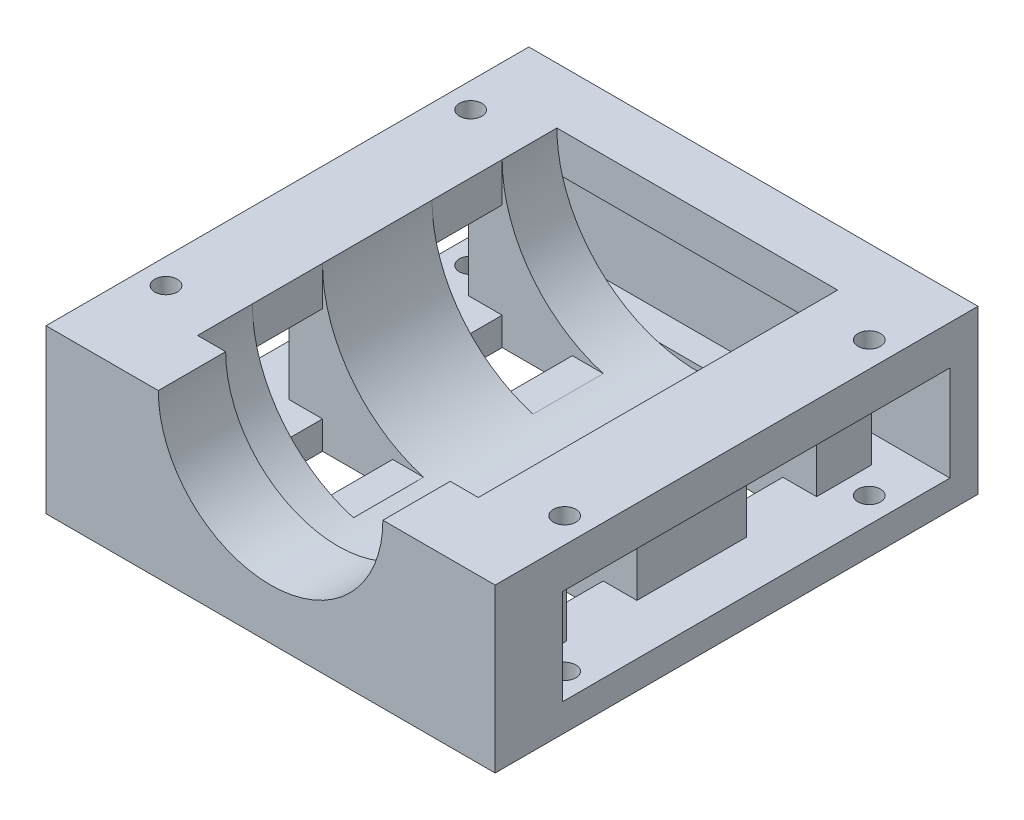
SolidWorks part; units mm, degrees
ref_plane "Front Plane" through (0, 0, 0) normal (0, 0, 1) x (1, 0, 0)
ref_plane "Top Plane" through (0, 0, 0) normal (0, 1, 0) x (1, 0, 0)
ref_plane "Right Plane" through (0, 0, 0) normal (1, 0, 0) x (0, 0, -1)
sketch "Sketch1" plane through (0, 0, 0) normal (0, 0, 1) x (1, 0, 0)
  line L0 (0, 0) -> (80, 0)
  line L1 (80, 0) -> (80, 5)
  line L2 (80, 5) -> (71, 5)
  line L3 (71, 5) -> (71, 22)
  line L4 (80, 29) -> (65, 29)
  line L7 (15, 29) -> (0, 29)
  line L8 (9, 22) -> (9, 5)
  line L9 (9, 5) -> (0, 5)
  line L10 (0, 5) -> (0, 0)
  line L12 (0, 29) -> (0, 22)
  line L13 (0, 22) -> (9, 22)
  line L14 (80, 29) -> (80, 22)
  line L15 (80, 22) -> (71, 22)
  arc A0 (15, 29) -> (65, 29) centre (40, 29) ccw
  dimension "D1" = 50
  dimension "D2" = 9
  dimension "D3" = 5
  dimension "D4" = 7
  dimension "D5" = 15
  dimension "D6" = 17
extrude "Boss-Extrude1" add sketch "Sketch1" along normal blind 64
ref_plane "Plane1" through (0, 0, 64) normal (0, 0, 1) x (1, 0, 0)
sketch "Sketch2" plane through (0, 0, 64) normal (0, 0, 1) x (1, 0, 0)
  line L0 (60, 29) -> (80, 29)
  line L1 (0, 0) -> (80, 0)
  line L2 (0, 0) -> (0, 29)
  line L3 (0, 29) -> (20, 29)
  line L4 (80, 0) -> (80, 29)
  line L5 (40, 0) -> (40, 29) construction
  arc A0 (20, 29) -> (60, 29) centre (40, 29) ccw
  dimension "D1" = 40
extrude "Boss-Extrude2" add sketch "Sketch2" along normal blind 12
ref_plane "Plane2" through (0, 29, 0) normal (0, 1, 0) x (1, 0, 0)
sketch "Sketch3" plane through (0, 29, 0) normal (0, 1, 0) x (1, 0, 0)
  line L0 (15, -64) -> (15, 0) construction
  line L1 (15, -9.75) -> (27.5, -9.75)
  line L2 (15, -9.75) -> (15, -22.25)
  line L3 (15, -22.25) -> (27.5, -22.25)
  line L4 (27.5, -9.75) -> (27.5, -22.25)
  line L5 (40, 0) -> (40, -64) construction
  line L6 (65, 0) -> (15, 0) construction
  line L7 (-55, -64) -> (55, -64) construction
  line L8 (40, -32) -> (15, -32) construction
  line L9 (15, 0) -> (65, -64) construction
  line L10 (65, 0) -> (15, -64) construction
  line L11 (15, -32) -> (40, 0) construction
  line L12 (27.5, -16) -> (15, -16) construction
  line L13 (65, -64) -> (65, 0) construction
  line L14 (65, -64) -> (60, -64) construction
  line L15 (65, -22.25) -> (52.5, -22.25)
  line L16 (52.5, -9.75) -> (52.5, -22.25)
  line L17 (65, -9.75) -> (52.5, -9.75)
  line L18 (65, -9.75) -> (65, -22.25)
  line L19 (15, -41.75) -> (27.5, -41.75)
  line L20 (27.5, -54.25) -> (27.5, -41.75)
  line L21 (15, -54.25) -> (27.5, -54.25)
  line L22 (15, -54.25) -> (15, -41.75)
  line L23 (65, -54.25) -> (65, -41.75)
  line L24 (65, -54.25) -> (52.5, -54.25)
  line L25 (52.5, -54.25) -> (52.5, -41.75)
  line L26 (65, -41.75) -> (52.5, -41.75)
  point P23 (15, -16)
extrude "Cut-Extrude1" cut sketch "Sketch3" against normal up to surface (29 mm away) up to face at (40, 0, 38)
ref_plane "Plane3" through (15, 0, 0) normal (1, 0, 0) x (0, 0, -1)
sketch "Sketch5" plane through (15, 0, 0) normal (1, 0, 0) x (0, 0, -1)
  line L0 (-54.25, 0) -> (-54.25, 29) construction
  line L1 (-54.25, 22) -> (-41.75, 22)
  line L2 (-54.25, 22) -> (-54.25, 5)
  line L3 (-54.25, 5) -> (-41.75, 5)
  line L4 (-41.75, 22) -> (-41.75, 5)
  line L5 (-41.75, 0) -> (-41.75, 29) construction
  line L8 (-54.25, 22) -> (-54.25, 29) construction
  line L9 (-54.25, 0) -> (-54.25, 5) construction
  line L16 (-22.25, 22) -> (-9.75, 22)
  line L17 (-22.25, 22) -> (-22.25, 5)
  line L18 (-22.25, 5) -> (-9.75, 5)
  line L19 (-9.75, 22) -> (-9.75, 5)
  line L20 (-22.25, 0) -> (-22.25, 7.3494) construction
  line L21 (-9.75, 0) -> (-9.75, 29) construction
  dimension "D1" = 7
  dimension "D2" = 5
extrude "Cut-Extrude2" cut sketch "Sketch5" against normal up to surface and the other way up to surface up to face at (9, 13.5, 32) other way up to face at (71, 13.5, 32)
ref_plane "Plane4" through (0, 0, 0) normal (0, -1, 0) x (-1, 0, 0)
sketch "Sketch6" plane through (0, 0, 0) normal (0, -1, 0) x (-1, 0, 0)
  line L0 (-4.8728, -32) -> (0, -32) construction
  line L1 (-15, 0) -> (-15, -76) construction
  line L2 (-15, 15.95) -> (-15, -15.95) construction
  line L3 (0, -76) -> (-80, -76) construction
  line L4 (-15, -54.25) -> (0, -64) construction
  line L5 (-27.5, -54.25) -> (-15, -54.25) construction
  line L7 (0, -76) -> (0, 0) construction
  line L9 (0, 0) -> (-80, 0) construction
  line L10 (-40, -76) -> (-40, 0) construction
  line L11 (0, -64) -> (-15, -64) construction
  line L12 (-55, -64) -> (55, -64) construction
  line L13 (0, -64) -> (-15, 0) construction
  line L14 (0, -64) -> (-8.9998, -64) construction
  line L15 (-8.9998, -64) -> (-8.9998, -54.25) construction
  line L16 (-8.9998, -54.25) -> (0, -54.25) construction
  line L17 (0, -54.25) -> (-8.9998, -64) construction
  line L18 (0, -64) -> (-8.9998, -54.25) construction
  circle A0 centre (-4.4999, -59.125) radius 2
  circle A1 centre (-4.4999, -4.875) radius 2
  circle A2 centre (-75.5001, -4.875) radius 2
  circle A3 centre (-75.5001, -59.125) radius 2
  point P13 (-4.4999, -59.125)
  dimension "D1" = 4
extrude "Cut-Extrude3" cut sketch "Sketch6" against normal up to surface (29 mm away) up to face at (67, 29, 40.8)
ref_plane "Plane5" through (0, 0, 0) normal (0, 0, -1) x (-1, 0, 0)
sketch "Sketch7" plane through (0, 0, 0) normal (0, 0, -1) x (-1, 0, 0)
  line L1 (-80, 0) -> (0, 0)
  line L2 (-80, 0) -> (-80, 29)
  line L3 (-80, 29) -> (0, 29)
  line L4 (0, 0) -> (0, 29)
extrude "Boss-Extrude3" add sketch "Sketch7" along normal blind 10
ref_plane "Plane6" through (80, 0, 0) normal (1, 0, 0) x (0, 0, -1)
sketch "Sketch8" plane through (80, 0, 0) normal (1, 0, 0) x (0, 0, -1)
  line L0 (0, 5) -> (10, 5) construction
  line L1 (0, 22) -> (5, 22)
  line L2 (0, 22) -> (0, 5)
  line L3 (0, 5) -> (5, 5)
  line L4 (5, 22) -> (5, 5)
  line L5 (10, 29) -> (10, 0) construction
  line L6 (0, 22) -> (10, 5) construction
  line L8 (0, 5) -> (10, 22) construction
  point P2 (5, 13.5)
  point P12 (5, 13.5)
extrude "Cut-Extrude4" cut sketch "Sketch8" against normal up to surface (80 mm away) up to face at (0, 14.5, 33)
